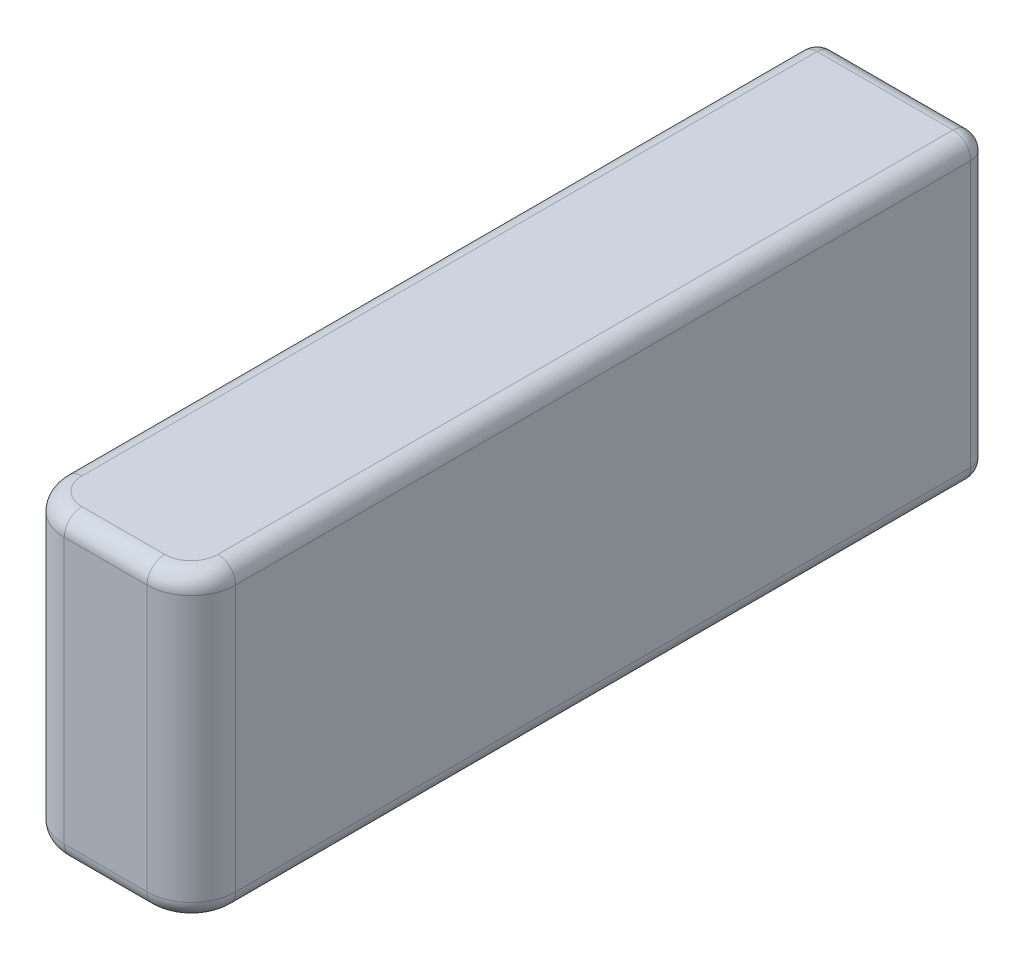
SolidWorks part; units mm, degrees
ref_plane "Plan de face" through (0, 0, 0) normal (0, 0, 1) x (1, 0, 0)
ref_plane "Plan de dessus" through (0, 0, 0) normal (0, 1, 0) x (1, 0, 0)
ref_plane "Plan de droite" through (0, 0, 0) normal (1, 0, 0) x (0, 0, -1)
sketch "Esquisse1" plane through (0, 0, 0) normal (0, 0, 1) x (1, 0, 0)
  line L1 (0, 0) -> (19.35, 0)
  line L2 (0, 0) -> (0, 34)
  line L3 (0, 34) -> (19.35, 34)
  line L4 (19.35, 0) -> (19.35, 34)
  dimension "D1" = 19.35
  dimension "D2" = 34
extrude "Boss.-Extru.1" add sketch "Esquisse1" along normal blind 90
fillet "Congé1" radius 2 10 edges at (9.675, 34, 90) (9.675, 0, 90) (19.35, 34, 45) (9.675, 34, 0) (0, 34, 45) (19.35, 0, 45) (0, 0, 45) (9.675, 0, 0) (19.35, 17, 0) (0, 17, 0)
fillet "Congé2" radius 5 6 edges at (0.5858, 0.5858, 89.4142) (0.5858, 33.4142, 89.4142) (18.7642, 33.4142, 89.4142) (18.7642, 0.5858, 89.4142) (19.35, 17, 90) (0, 17, 90)
